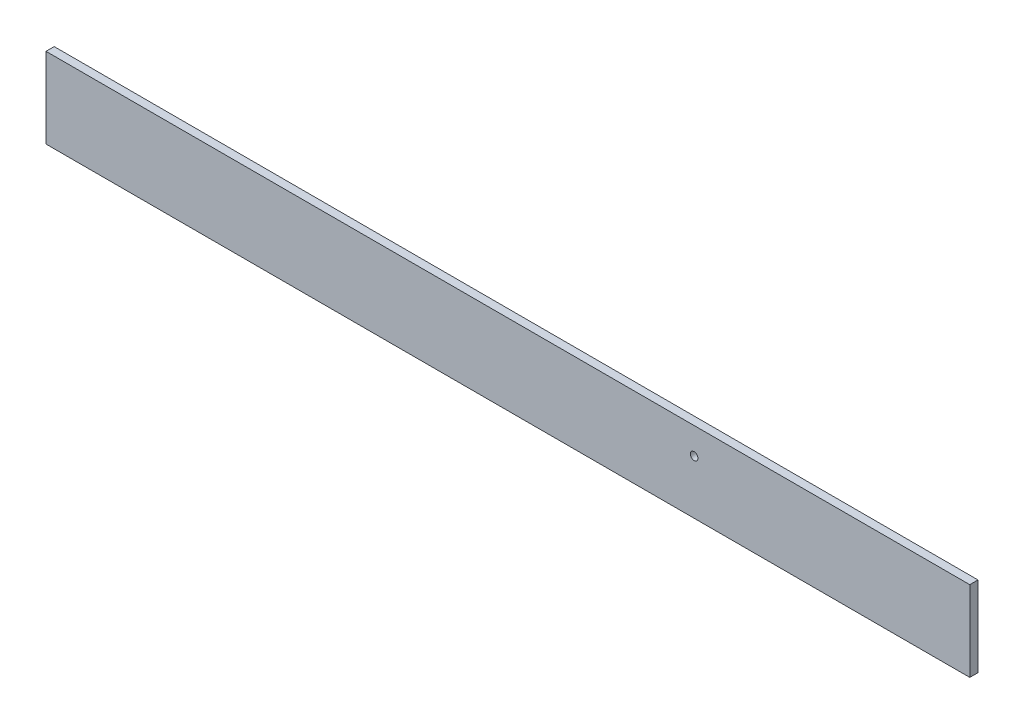
SolidWorks part; units mm, degrees
ref_plane "Front Plane" through (0, 0, 0) normal (0, 0, 1) x (1, 0, 0)
ref_plane "Top Plane" through (0, 0, 0) normal (0, 1, 0) x (1, 0, 0)
ref_plane "Right Plane" through (0, 0, 0) normal (1, 0, 0) x (0, 0, -1)
sketch "Sketch2" plane through (0, 0, 0) normal (0, 0, 1) x (1, 0, 0)
  line L1 (-253, -22) -> (253, -22)
  line L2 (-253, -22) -> (-253, 22)
  line L3 (-253, 22) -> (253, 22)
  line L4 (253, -22) -> (253, 22)
  line L5 (-253, -22) -> (253, 22) construction
  line L6 (-253, 22) -> (253, -22) construction
  circle A0 centre (102, 7.5) radius 2.1 construction
  circle A1 centre (102, 7.5) radius 2.1
  point P0 (0, 0)
  dimension "D1" = 44
  dimension "D2" = 506
extrude "Boss-Extrude1" add sketch "Sketch2" along normal blind 4.5
